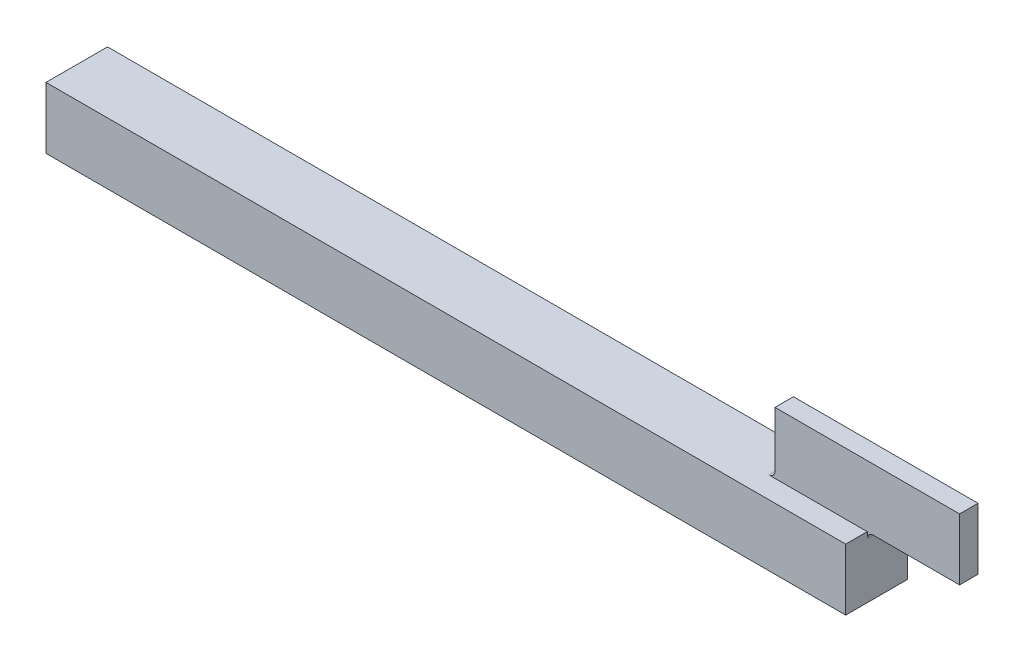
SolidWorks part; units mm, degrees
ref_plane "Plan de face" through (0, 0, 0) normal (0, 0, 1) x (1, 0, 0)
ref_plane "Plan de dessus" through (0, 0, 0) normal (0, 1, 0) x (1, 0, 0)
ref_plane "Plan de droite" through (0, 0, 0) normal (1, 0, 0) x (0, 0, -1)
sketch "Esquisse1" plane through (0, 0, 0) normal (0, 1, 0) x (1, 0, 0)
  line L1 (65, -5) -> (-65, -5)
  line L2 (65, -5) -> (65, 5)
  line L3 (65, 5) -> (-65, 5)
  line L4 (-65, -5) -> (-65, 5)
  line L5 (65, -5) -> (-65, 5) construction
  line L6 (65, 5) -> (-65, -5) construction
  point P0 (0, 0)
  dimension "D1" = 130
  dimension "D2" = 10
extrude "Boss.-Extru.1" add sketch "Esquisse1" along normal blind 10
sketch "Esquisse2" plane through (0, 10, 0) normal (0, 1, 0) x (1, 0, 0)
  line L0 (65, -5) -> (65, 5) construction
  line L1 (80, -1.5) -> (50, -1.5)
  line L2 (80, -1.5) -> (80, 1.5)
  line L3 (80, 1.5) -> (50, 1.5)
  line L4 (50, -1.5) -> (50, 1.5)
  line L5 (80, -1.5) -> (50, 1.5) construction
  line L6 (80, 1.5) -> (50, -1.5) construction
  point P0 (65, 0)
  dimension "D1" = 30
  dimension "D2" = 3
extrude "Boss.-Extru.2" add sketch "Esquisse2" along normal blind 10
fillet "Congé1" radius 1 2 edges at (50, 10, 0) (65, 10, 0)
